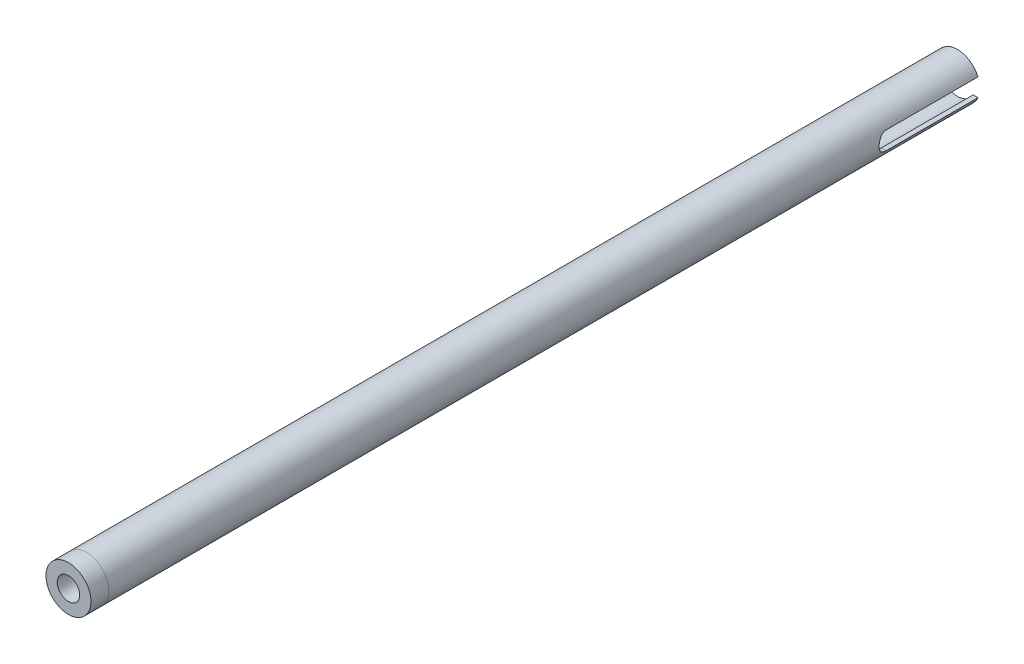
SolidWorks part; units mm, degrees
ref_plane "Front Plane" through (0, 0, 0) normal (0, 0, 1) x (1, 0, 0)
ref_plane "Top Plane" through (0, 0, 0) normal (0, 1, 0) x (1, 0, 0)
ref_plane "Right Plane" through (0, 0, 0) normal (1, 0, 0) x (0, 0, -1)
sketch "Axis" plane through (0, 0, 0) normal (0, 1, 0) x (1, 0, 0)
  line L0 (0, 0) -> (0, 313.6923) construction
  line L1 (0, 0) -> (0, -34.925) construction
  line L2 (0, 313.6923) -> (-7.9375, 313.6923) construction
  line L3 (0, 342.1316) -> (-10.3188, 305.1605) construction
  dimension "D1" = 34.925
  dimension "D2" = 7.9375
sketch "Sketch1" plane through (0, 0, 0) normal (0, 0, 1) x (1, 0, 0)
  line L0 (-7.9375, 0) -> (7.9375, 0) construction
  line L1 (-7.2748, 3.175) -> (7.2748, 3.175)
  line L2 (-7.2748, -3.175) -> (7.2748, -3.175)
  circle A0 centre (0, 0) radius 7.9375
  circle A1 centre (0, 0) radius 6.4135
  circle A2 centre (0, 0) radius 3.9688
  dimension "D1" = 15.875
  dimension "D3" = 7.9375
  dimension "D2" = 1.524
  dimension "D4" = 6.35
extrude "Threaded insert 1-1" add sketch "Sketch1" against normal blind 6.35 contours A2 L1 A1 | A1 L1 A0 | A2 L0 A1 L1 | A1 L0 A0 L1 | L0 A1 L2 A0 | L0 A2 L2 A1 | A2 L2 A1 | A1 L2 A0 | L0 A1 L2 A2 | L0 A0 L2 A1 | A0 L0 A1 L1 | A1 L0 A2 L1 region at (4.7887, 1.6543, 0) region at (4.7887, -1.6543, 0) region at (6.9234, 1.6163, 0) region at (6.9234, -1.6163, 0) region at (-4.7887, -1.6543, 0) region at (-4.7887, 1.6543, 0) region at (0, 4.6159, 0) region at (0, -4.6159, 0) region at (0, 6.5666, 0) region at (6.4237, -3.3281, 0) region at (-6.9234, -1.6163, 0) region at (-6.9234, 1.6163, 0)
extrude "Threaded insert 1-2" add sketch "Sketch1<3>" against normal blind 9.525 from surface contours A2 L1 A1 | A2 L0 A1 L1 | L0 A2 L2 A1 | A2 L2 A1 | L0 A1 L2 A2 | A1 L0 A2 L1 region at (4.7887, 1.6543, 0) region at (4.7887, -1.6543, 0) region at (-4.7887, -1.6543, 0) region at (-4.7887, 1.6543, 0) region at (0, 4.6159, 0) region at (0, -4.6159, 0) starting at face at (7.9375, 0, -6.35)
sketch "Sketch1<3>" plane through (0, 0, 0) normal (0, 0, 1) x (1, 0, 0) same geometry as "Sketch1"
extrude "A-arm tube" add sketch "Sketch1<4>" against normal up to vertex (313.6923 mm away) from surface separate body contours A1 L1 A0 | A1 L0 A0 L1 | L0 A1 L2 A0 | A1 L2 A0 | L0 A0 L2 A1 | A0 L0 A1 L1 region at (6.9234, 1.6163, 0) region at (6.9234, -1.6163, 0) region at (0, 6.5666, 0) region at (6.4237, -3.3281, 0) region at (-6.9234, -1.6163, 0) region at (-6.9234, 1.6163, 0) up to point (0, 0, -313.6923) starting at face at (6.4135, 0, -6.35)
sketch "Sketch1<4>" plane through (0, 0, 0) normal (0, 0, 1) x (1, 0, 0) same geometry as "Sketch1"
extrude "Apex slot" cut sketch "Sketch1<5>" along normal blind 35.56 from surface contours A0 L0 A1 L1 | L0 A0 L2 A1 | A1 L0 A0 L1 | L0 A1 L2 A0 region at (6.9234, 1.6163, 0) region at (6.9234, -1.6163, 0) region at (-6.9234, -1.6163, 0) region at (-6.9234, 1.6163, 0) starting at face at (6.4135, 0, -313.6923)
sketch "Sketch1<5>" plane through (0, 0, 0) normal (0, 0, 1) x (1, 0, 0) same geometry as "Sketch1"
fillet "Fillet1" radius 3.175 4 edges at (-6.4237, 3.175, -278.1323) (-6.4237, -3.175, -278.1323) (6.4237, -3.175, -278.1323) (6.4237, 3.175, -278.1323)
equation "\"tube diameter\"= 5 / 8"
equation "\"tube thickness\"= .06"
equation "\"apex thickness\"= .25"
equation "\"tube slot\"= 1.4"
equation "\"D1@Sketch1\"=\"tube diameter\""
equation "\"D2@Sketch1\"=\"tube thickness\""
equation "\"threaded insert hole\"= .3125"
equation "\"D3@Sketch1\"=\"threaded insert hole\""
equation "\"D4@Sketch1\"=\"apex thickness\""
equation "\"D1@Apex slot\" = \"tube slot\""
equation "\"D1@Fillet1\"=\"apex thickness\"/2"
equation "\"D2@Axis\"=\"tube diameter\"/2"
